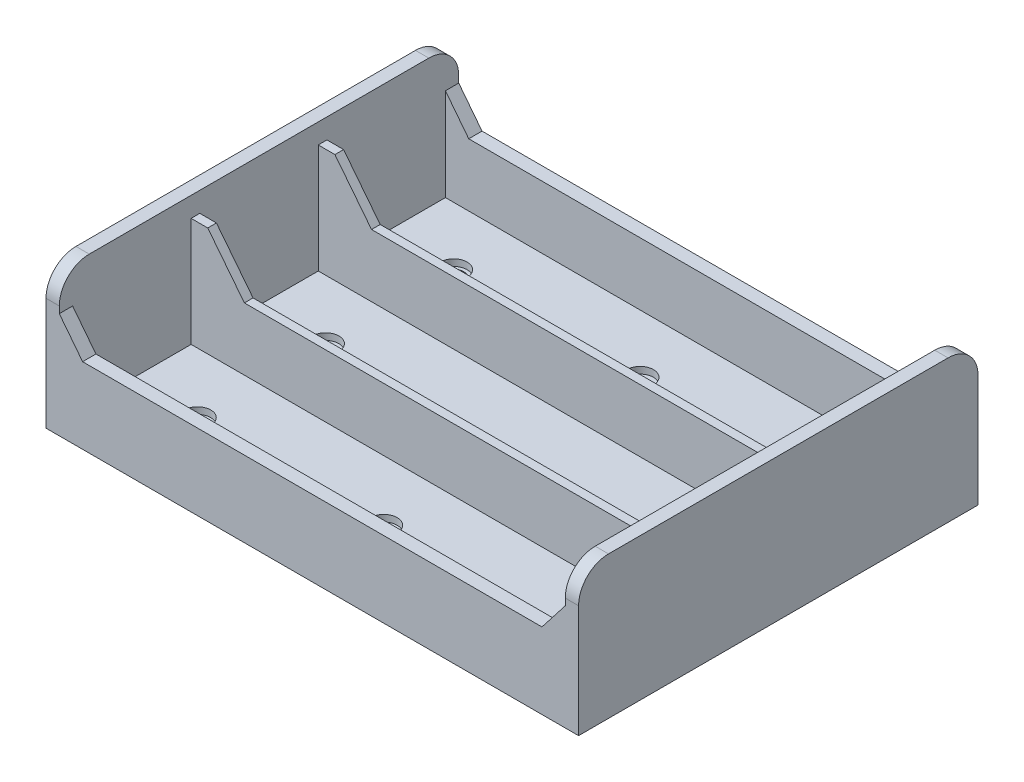
SolidWorks part; units mm, degrees
ref_plane "前视基准面" through (0, 0, 0) normal (0, 0, 1) x (1, 0, 0)
ref_plane "上视基准面" through (0, 0, 0) normal (0, 1, 0) x (1, 0, 0)
ref_plane "右视基准面" through (0, 0, 0) normal (1, 0, 0) x (0, 0, -1)
sketch "草图1" plane through (0, 0, 0) normal (0, 1, 0) x (1, 0, 0)
  line L1 (-37.3246, 19.6411) -> (42.6754, 19.6411)
  line L2 (-37.3246, 19.6411) -> (-37.3246, -40.3589)
  line L3 (-37.3246, -40.3589) -> (42.6754, -40.3589)
  line L4 (42.6754, 19.6411) -> (42.6754, -40.3589)
  dimension "D1" = 80
  dimension "D2" = 60
extrude "凸台-拉伸1" add sketch "草图1" along normal blind 21.4
fillet "圆角1" radius 4.5 2 edges at (2.6754, 21.4, -19.6411) (2.6754, 21.4, 40.3589)
sketch "草图2" plane through (0, 0, 40.3589) normal (0, 0, 1) x (1, 0, 0)
  line L0 (40.6754, 21.4) -> (-35.3246, 21.4)
  line L1 (-37.3246, 21.4) -> (42.6754, 21.4) construction
  line L2 (-35.3246, 21.4) -> (-35.3246, 15.9)
  line L3 (-35.3246, 15.9) -> (-31.8246, 11.4)
  line L4 (-31.8246, 11.4) -> (37.1754, 11.4)
  line L5 (37.1754, 11.4) -> (40.6754, 15.9)
  line L6 (40.6754, 15.9) -> (40.6754, 21.4)
  line L7 (-37.3246, 21.4) -> (-37.3246, 16.9) construction
  line L8 (42.6754, 16.9) -> (42.6754, 21.4) construction
  line L9 (-37.3246, 16.9) -> (-37.3246, 0) construction
  line L10 (42.6754, 16.9) -> (42.6754, 0) construction
  point P0 (0, 0)
  dimension "D1" = 2
  dimension "D2" = 2
  dimension "D3" = 10
  dimension "D4" = 5.5
  dimension "D5" = 5.5
  dimension "D6" = 5.5
extrude "切除-拉伸1" cut sketch "草图2" against normal through all
sketch "草图3" plane through (0, 21.4, 0) normal (0, 1, 0) x (1, 0, 0)
  line L0 (-35.3246, 15.1411) -> (-35.3246, 19.6411) construction
  line L1 (-35.3246, 17.6411) -> (40.6754, 17.6411)
  line L2 (-35.3246, 17.6411) -> (-35.3246, -38.3589)
  line L3 (-35.3246, -38.3589) -> (40.6754, -38.3589)
  line L4 (40.6754, 17.6411) -> (40.6754, -38.3589)
  line L5 (40.6754, 19.6411) -> (40.6754, -40.3589) construction
  line L6 (-35.3246, 19.6411) -> (-31.8246, 19.6411) construction
  line L7 (-35.3246, -40.3589) -> (-31.8246, -40.3589) construction
  dimension "D1" = 2
  dimension "D2" = 2
extrude "切除-拉伸2" cut sketch "草图3" against normal blind 19.4
sketch "草图4" plane through (0, 2, 0) normal (0, 1, 0) x (1, 0, 0)
  line L0 (-35.3246, 15.1411) -> (-35.3246, -35.8589) construction
  line L1 (-35.3246, -0.1589) -> (40.6754, -0.1589)
  line L2 (-35.3246, -0.1589) -> (-35.3246, -1.4589)
  line L3 (-35.3246, -1.4589) -> (40.6754, -1.4589)
  line L4 (40.6754, -0.1589) -> (40.6754, -1.4589)
  line L5 (40.6754, -38.3589) -> (40.6754, 17.6411) construction
  line L6 (-35.3246, 17.6411) -> (-35.3246, -38.3589) construction
  line L7 (-35.3246, -19.2589) -> (40.6754, -19.2589)
  line L8 (-35.3246, -19.2589) -> (-35.3246, -20.5589)
  line L9 (-35.3246, -20.5589) -> (40.6754, -20.5589)
  line L10 (40.6754, -19.2589) -> (40.6754, -20.5589)
  line L11 (40.6754, 15.1411) -> (40.6754, -35.8589) construction
  line L12 (-31.8246, 17.6411) -> (37.1754, 17.6411) construction
  dimension "D1" = 17.8
  dimension "D3" = 17.8
  dimension "D4" = 17.8
extrude "凸台-拉伸2" add sketch "草图4" along normal blind 16.4
sketch "草图5" plane through (0, 0, 20.5589) normal (0, 0, 1) x (1, 0, 0)
  line L0 (-32.825, 18.4) -> (-27.3246, 11.4)
  line L1 (-35.3246, 18.4) -> (40.6754, 18.4) construction
  line L2 (-31.8246, 11.4) -> (37.1754, 11.4) construction
  line L3 (-27.3246, 11.4) -> (32.6754, 11.4)
  line L4 (32.6754, 11.4) -> (38.1754, 18.4)
  line L5 (38.1754, 18.4) -> (-32.825, 18.4)
  line L6 (-37.3246, 21.4) -> (-37.3246, 16.9) construction
  line L7 (42.6754, 16.9) -> (42.6754, 21.4) construction
  line L8 (-37.3246, 16.9) -> (-37.3246, 0) construction
  line L9 (42.6754, 16.9) -> (42.6754, 0) construction
  dimension "D1" = 4.4996
  dimension "D2" = 4.5
  dimension "D3" = 10
  dimension "D4" = 10
extrude "切除-拉伸3" cut sketch "草图5" against normal blind 26.4
sketch "草图6" plane through (0, 2, 0) normal (0, 1, 0) x (1, 0, 0)
  line L0 (-31.8246, 19.6411) -> (37.1754, 19.6411) construction
  line L1 (-37.3246, 19.6411) -> (-37.3246, 15.1411) construction
  line L2 (42.6754, -35.8589) -> (42.6754, 15.1411) construction
  circle A0 centre (2.6754, 8.8911) radius 1.25
  circle A1 centre (2.6754, -29.6089) radius 1.25
  circle A2 centre (-25.3246, 8.8911) radius 1.5
  circle A3 centre (30.6754, 8.8911) radius 1.5
  circle A4 centre (30.6754, -10.8291) radius 1.5
  circle A5 centre (30.6754, -29.6089) radius 1.5
  circle A6 centre (-25.3246, -29.6089) radius 1.5
  circle A7 centre (-25.3246, -10.3589) radius 1.5
  point P16 (0, 0)
  point P17 (0, 0)
  point P18 (0, 0)
  point P19 (0, 0)
  point P26 (0, 0)
  point P27 (2.6754, 19.6411)
  dimension "D1" = 3
  dimension "D3" = 2.5
  dimension "D2" = 38.5
  dimension "D4" = 19.25
  dimension "D5" = 10.75
  dimension "D6" = 12
  dimension "D7" = 12
extrude "切除-拉伸4" cut sketch "草图6" against normal up to next
sketch "草图7" plane through (0, 2, 0) normal (0, 1, 0) x (1, 0, 0)
  circle A1 centre (-25.3246, 8.8911) radius 2
  circle A2 centre (2.6754, 8.8911) radius 2
  circle A3 centre (30.6754, 8.8911) radius 2
  circle A4 centre (-25.3246, -10.3589) radius 2
  circle A5 centre (30.6754, -10.8291) radius 2
  circle A6 centre (-25.3246, -29.6089) radius 2
  circle A7 centre (2.6754, -29.6089) radius 2
  circle A8 centre (30.6754, -29.6089) radius 2
  dimension "D1" = 4
extrude "切除-拉伸5" cut sketch "草图7" against normal blind 1
